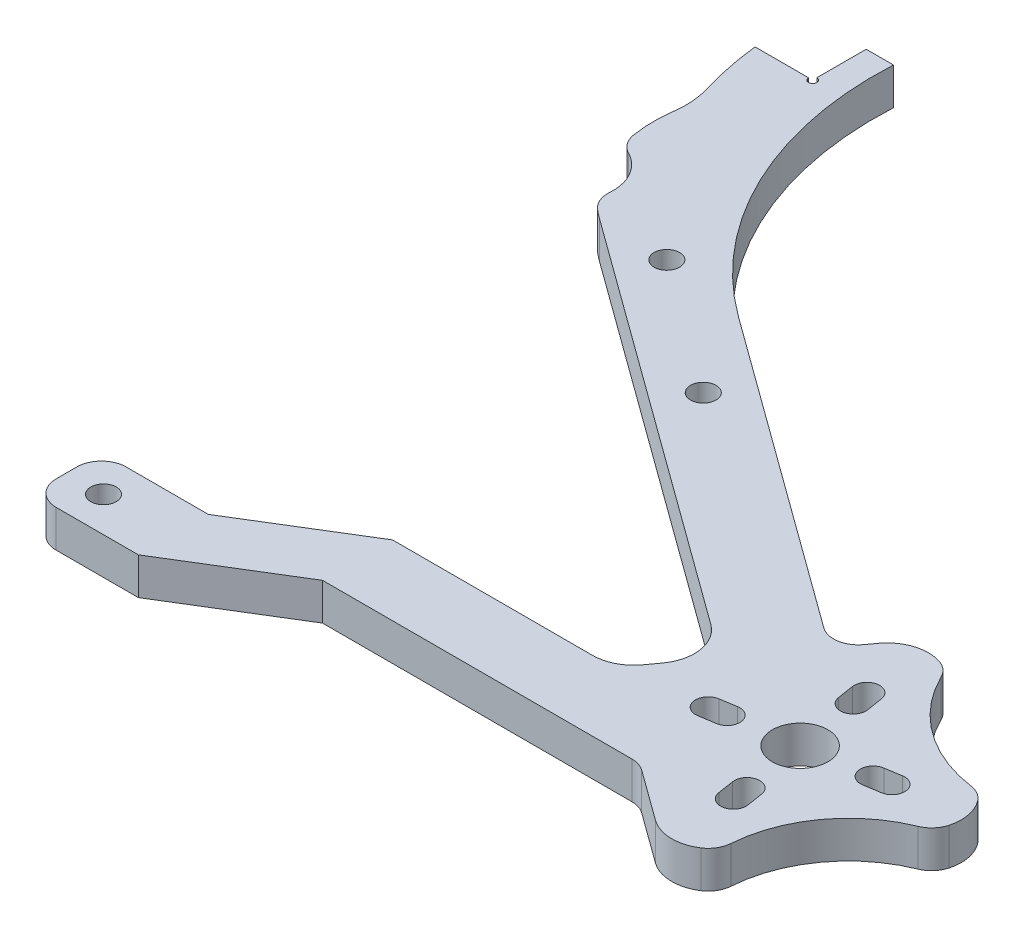
SolidWorks part; units mm, degrees
material "PPS"
ref_plane "前视基准面" through (0, 0, 0) normal (0, 0, 1) x (1, 0, 0)
ref_plane "上视基准面" through (0, 0, 0) normal (0, 1, 0) x (1, 0, 0)
ref_plane "右视基准面" through (0, 0, 0) normal (1, 0, 0) x (0, 0, -1)
sketch "草图3" plane through (0, 0, 0) normal (0, 1, 0) x (1, 0, 0)
  line L0 (0, 0) -> (35.4735, 0) construction
  line L1 (0, 0) -> (62.3757, -45.3186) construction
  line L2 (41.1319, -24.0128) -> (94.6944, -62.9282)
  line L3 (94.6944, -62.9282) -> (100.1314, -55.4448)
  line L4 (100.1314, -55.4448) -> (122.7839, -71.9028)
  line L5 (122.7839, -71.9028) -> (106.3259, -94.5552)
  line L6 (83.6734, -78.0972) -> (106.3259, -94.5552) construction
  line L9 (77.9994, -109.7251) -> (128.6275, -40.0415) construction
  line L11 (103.2286, -75) -> (90.242, -77.0569) construction
  line L13 (110.8832, -73.7876) -> (112.8586, -73.4748) construction
  line L14 (110.6408, -72.2567) -> (112.6161, -71.9438)
  line L15 (111.1257, -75.3185) -> (113.1011, -75.0057)
  line L16 (102.0163, -67.3454) -> (101.7034, -65.37) construction
  line L17 (103.5472, -67.1029) -> (103.2343, -65.1276)
  line L18 (100.4854, -67.5879) -> (100.1725, -65.6125)
  line L19 (95.5741, -76.2124) -> (93.5987, -76.5252) construction
  line L20 (95.8165, -77.7433) -> (93.8412, -78.0562)
  line L21 (95.3316, -74.6815) -> (93.3562, -74.9943)
  line L22 (104.441, -82.6546) -> (104.7539, -84.63) construction
  line L23 (102.9101, -82.8971) -> (103.223, -84.8724)
  line L24 (105.9719, -82.4121) -> (106.2848, -84.3875)
  line L36 (68.8077, -72) -> (90.242, -72) construction
  line L49 (89.1104, -70.6138) -> (83.6734, -78.0972)
  line L50 (35.5479, -31.6984) -> (89.1104, -70.6138)
  line L51 (83.6734, -78.0972) -> (30, -78.0972) construction
  line L52 (30, -78.0972) -> (30, -86.5972) construction
  line L53 (30, -86.5972) -> (95.3727, -86.5972) construction
  line L54 (95.3727, -86.5972) -> (106.3259, -94.5552)
  line L55 (83.6734, -78.0972) -> (56.8367, -78.0972)
  line L56 (95.3727, -86.5972) -> (56.8367, -86.5972)
  line L57 (56.8367, -78.0972) -> (42.9738, -86.5972)
  line L58 (42.9738, -86.5972) -> (30, -86.5972)
  line L59 (56.8367, -86.5972) -> (42.9738, -95.0972)
  line L60 (30, -86.5972) -> (30, -95.0972)
  line L61 (30, -95.0972) -> (42.9738, -95.0972)
  circle A5 centre (103.2286, -75) radius 3.375
  arc A6 (110.6408, -72.2567) -> (111.1257, -75.3185) centre (110.8832, -73.7876) ccw
  arc A7 (113.1011, -75.0057) -> (112.6161, -71.9438) centre (112.8586, -73.4748) ccw
  arc A8 (103.5472, -67.1029) -> (100.4854, -67.5879) centre (102.0163, -67.3454) cw
  arc A9 (100.1725, -65.6125) -> (103.2343, -65.1276) centre (101.7034, -65.37) cw
  arc A10 (95.8165, -77.7433) -> (95.3316, -74.6815) centre (95.5741, -76.2124) ccw
  arc A11 (93.3562, -74.9943) -> (93.8412, -78.0562) centre (93.5987, -76.5252) ccw
  arc A12 (102.9101, -82.8971) -> (105.9719, -82.4121) centre (104.441, -82.6546) cw
  arc A13 (106.2848, -84.3875) -> (103.223, -84.8724) centre (104.7539, -84.63) cw
  arc A16 (41.1319, -24.0128) -> (35.5479, -31.6984) centre (38.3399, -27.8556) ccw
  circle A17 centre (103.2286, -75) radius 66.25 construction
  circle A18 centre (44.0442, -32) radius 1.55
  circle A19 centre (60.2246, -43.7557) radius 1.55
  circle A20 centre (34.5, -90.85) radius 1.55
  point P11 (114.5549, -83.229)
  point P20 (111.8709, -73.6312)
  point P27 (101.8598, -66.3577)
  point P35 (94.5864, -76.3688)
  point P42 (104.5974, -83.6423)
  point P54 (94.9997, -86.3262)
  point P59 (0, 0)
  point P60 (0, 0)
  point P66 (0, 0)
  point P69 (30, -90.8472)
  point P70 (0, 0)
  dimension "D2" = 45
  dimension "D3" = 6.75
  dimension "D4" = 1.55
  dimension "D7" = 14
  dimension "D11" = 132.5
  dimension "D12" = 3.1
  dimension "D16" = 3.1
  dimension "D1" = 36
  dimension "D5" = 2
  dimension "D6" = 7.75
  dimension "D8" = 14
  dimension "D9" = 4.75
  dimension "D10" = 75
  dimension "D13" = 32
  dimension "D14" = 20
  dimension "D15" = 8.5
  dimension "D17" = 34.5
  dimension "D18" = 4.5
  dimension "D19" = 90.85
  dimension "D22" = 72
extrude "凸台-拉伸1" add sketch "草图3" along normal blind 4.5
fillet "圆角-美观1" radius 5 5 edges at (100.1314, 2.25, 55.4448) (122.7839, 2.25, 71.9028) (89.1104, 2.25, 70.6138) (106.3259, 2.25, 94.5552) (83.6734, 2.25, 78.0972)
sketch "草图4" plane through (0, 4.5, 0) normal (0, 1, 0) x (1, 0, 0)
  line L0 (104.1765, -58.3837) -> (118.7388, -68.9638)
  line L1 (119.8449, -75.9478) -> (109.2648, -90.5101)
  line L3 (103.2286, -75) -> (124.6569, -90.5685) construction
  line L4 (103.2286, -75) -> (89.033, -94.5387) construction
  line L5 (87.7185, -81.0362) -> (102.2808, -91.6163)
  arc A2 (102.2808, -91.6163) -> (87.7185, -81.0362) centre (86.1651, -98.4859) ccw
  arc A8 (118.7388, -68.9638) -> (104.1765, -58.3837) centre (120.2922, -51.5141) cw
  arc A9 (119.8449, -75.9478) -> (109.2648, -90.5101) centre (124.6569, -90.5685) ccw
  line M2 (118.7388, -68.9638) -> (104.1765, -58.3837)
  line M12 (109.2648, -90.5101) -> (119.8449, -75.9478)
extrude "圆弧-美观2" cut sketch "草图4" against normal up to next contours A8 M2 | A9 M12 region at (110.8688, 4.5, 64.4842) region at (113.6066, 4.5, 82.54)
fillet "圆角-美观3" radius 3 8 edges at (104.1765, 2.25, 58.3837) (118.7388, 2.25, 68.9638) (119.8449, 2.25, 75.9478) (94.6944, 2.25, 62.9282) (109.2648, 2.25, 90.5101) (30, 2.25, 95.0972) (95.3727, 2.25, 86.5972) (30, 2.25, 86.5972)
sketch "草图5" plane through (0, 0, 0) normal (0, 1, 0) x (1, 0, 0)
  line L0 (0, 0) -> (158.8801, 0) construction
  line L1 (0, 0) -> (0, -78.2587) construction
  line L2 (29.255, -13.8932) -> (40.1931, -23.471) construction
  line L3 (27.0025, -4.25) -> (34, -4.25)
  line L4 (34, -4.25) -> (34, 2.25)
  line L5 (34, -3.25) -> (26.9026, -3.25) construction
  line L6 (34, 3.25) -> (34, -3.25) construction
  line L7 (37.3772, 3.25) -> (34, 3.25) construction
  line L8 (41.1319, -24.0128) -> (54.395, -33.649)
  line L9 (34, 2.25) -> (37.3109, 2.25)
  line L10 (35.5479, -31.6984) -> (85.0653, -67.6749) construction
  line L11 (41.1319, -24.0128) -> (35.5479, -31.6984)
  arc A0 (26.9026, -3.25) -> (28.5167, -11.6611) centre (68.8233, 0.4342) ccw construction
  arc A5 (41.1319, -24.0128) -> (40.1931, -23.471) centre (38.2952, -27.8445) ccw
  arc A7 (40.1931, -23.471) -> (35.5479, -31.6984) centre (38.3022, -27.8285) ccw construction
  arc A8 (35.5479, -31.6984) -> (28.8424, -15.919) centre (45.3379, -18.2237) cw
  arc A9 (28.8424, -15.919) -> (28.5167, -11.6611) centre (18.9386, -14.5353) ccw
  arc A11 (37.3772, 3.25) -> (54.395, -33.649) centre (78.8424, 0) ccw
  arc A12 (27.0025, -4.25) -> (28.5167, -11.6611) centre (68.8233, 0.4342) ccw
  arc A13 (29.8202, 19.4008) -> (29.8202, -19.4008) centre (91.9966, 0) ccw construction
  arc A14 (54.395, 33.649) -> (54.395, -33.649) centre (78.8424, 0) ccw construction
  arc A15 (29.9602, 19.3706) -> (29.9602, -19.3706) centre (67.3193, 0) ccw construction
  dimension "D1" = 3.25
  dimension "D2" = 3.25
  dimension "D3" = 34
  dimension "D4" = 1
  dimension "D5" = 1
extrude "机臂配合防旋转" add sketch "草图5" along normal up to surface (4.5 mm away) contours L7 A0 A9 A8 A7 A5 L8 region at (35.1434, 0, 16.2105) up to face at (60.2246, 4.5, 45.3057)
sketch "草图7" plane through (0, 0, 0) normal (0, 1, 0) x (1, 0, 0)
  circle A6 centre (28, -28) radius 3.15 construction
  circle A7 centre (28, -28) radius 5.5
  circle A8 centre (44.0442, -32) radius 1.55 construction
  dimension "D1" = 11
  dimension "D2" = 16.0442
  dimension "D3" = 4
extrude "减震球让位" cut sketch "草图7" along normal through all
fillet "圆角1" radius 3 2 edges at (33.2399, 2.25, 29.6714) (29.2815, 2.25, 22.6514)
sketch "草图8" plane through (0, 4.5, 0) normal (0, 1, 0) x (1, 0, 0)
  circle A0 centre (34, -4.25) radius 0.5
  dimension "D1" = 1
extrude "直角约束" cut sketch "草图8" against normal through all
